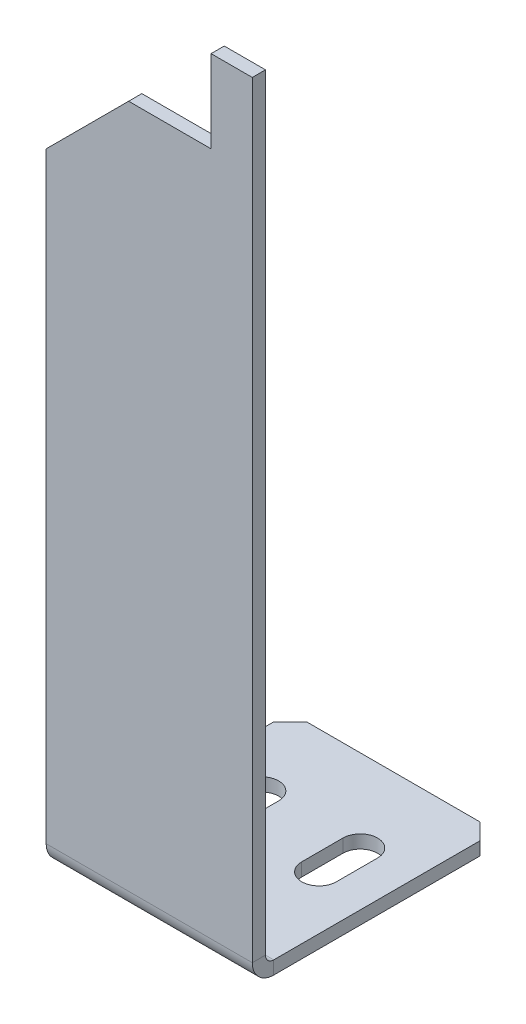
SolidWorks part; units mm, degrees
note: The reader was unsure of these and kept them because the rebuilt part matched: flange length of "邊線-凸緣1".
ref_plane "前基準面" through (0, 0, 0) normal (0, 0, 1) x (1, 0, 0)
ref_plane "上基準面" through (0, 0, 0) normal (0, 1, 0) x (1, 0, 0)
ref_plane "右基準面" through (0, 0, 0) normal (1, 0, 0) x (0, 0, -1)
sketch "草圖1" plane through (0, 0, 0) normal (0, 0, 1) x (1, 0, 0)
  line L0 (25, 0) -> (0, 0)
  dimension "D1" = 25
sheet metal parameters "鈑金1" thickness 1.6 parameters "D1"=1
base flange "基材-凸緣1" sketch "草圖1" end condition mid plane depth 28 reverse direction no thickness 1.6 reverse thickness direction no bend radius 1
sketch "草圖11" plane through (0, 0, 0) normal (0, -1, 0) x (1, 0, 0)
  line L0 (18.5, 1) -> (18.5, -4) construction
  line L1 (6.5, 1) -> (6.5, -4) construction
  line L2 (16.4, 1) -> (16.4, -4)
  line L3 (4.4, 1) -> (4.4, -4)
  line L4 (20.6, 1) -> (20.6, -4)
  line L5 (8.6, 1) -> (8.6, -4)
  line L6 (12.5, 14) -> (12.5, 8.9875) construction
  line L7 (25, 14) -> (0, 14) construction
  line L8 (25, -14) -> (0, -14) construction
  arc A0 (16.4, 1) -> (20.6, 1) centre (18.5, 1) cw
  arc A1 (16.4, -4) -> (20.6, -4) centre (18.5, -4) ccw
  arc A2 (4.4, 1) -> (8.6, 1) centre (6.5, 1) cw
  arc A3 (4.4, -4) -> (8.6, -4) centre (6.5, -4) ccw
  dimension "D5" = 10
  dimension "D3" = 12
  dimension "D4" = 5
  dimension "D1" = 2.1
  dimension "D2" = 2.1
extrude "除料-伸長2" cut sketch "草圖11" against normal up to next normal cut yes
edge flange "邊線-凸緣1" sketch "草圖9" flange angle 90 flange length 94 flange position material outside bend radius 1 thickness 1.6 relief rectangular parameters "D6"=10
sketch "草圖9" plane through (0, 1.6, 14) normal (0, 0, 1) x (1, 0, 0)
  line L0 (25, 0) -> (0, 0) construction
  line L1 (25, 0) -> (0, 0)
  line L2 (0, 0) -> (0, 94)
  line L3 (0, 94) -> (25, 94)
  line L4 (25, 94) -> (25, 0)
bend "邊線彎折1" bend radius 1 bend angle 90 parameters "D5"=1
sketch "草圖10" plane through (0, 0, 14) normal (0, 0, -1) x (-1, 0, 0)
  line L0 (-25, 2.6) -> (-25, 95.6) construction
  line L6 (0, 95.6) -> (-20, 95.6)
  line L7 (0, 95.6) -> (0, 85.6)
  line L8 (0, 85.6) -> (-20, 85.6)
  line L9 (-20, 95.6) -> (-20, 85.6)
  dimension "D1" = 5
  dimension "D2" = 10
extrude "除料-伸長1" cut sketch "草圖10" against normal up to next normal cut yes
chamfer "導角1" distance 10 angle 45 1 edges at (0, 85.6, 14.8)
chamfer "導角2" distance 2 angle 45 2 edges at (25, 0.8, -14) (0, 0.8, -14)
flat pattern "平板-型式1" [suppressed]
sketch "彎折-線1" plane through (0, 0, 0) normal (1, 0, 0) x (0, 0, -1)
bend of the flat pattern "平板-<邊線彎折1>1"
